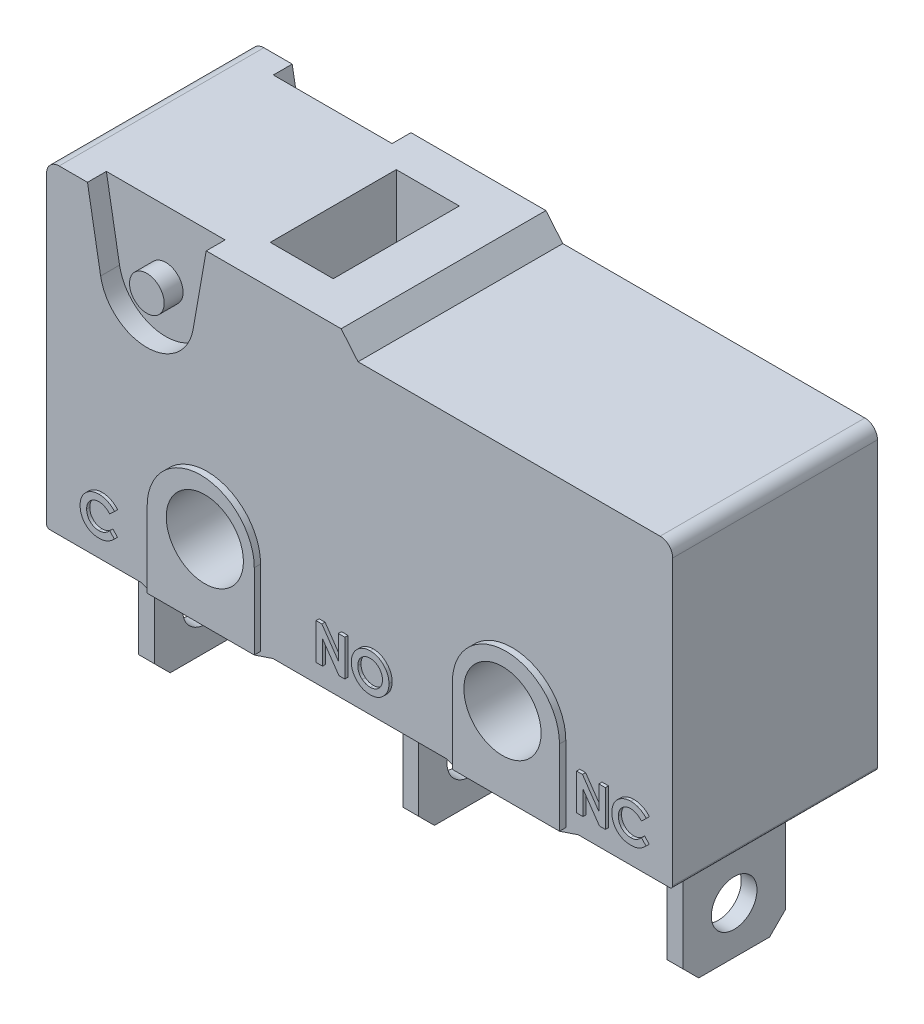
SolidWorks part; units mm, degrees
ref_plane "Front Plane" through (0, 0, 0) normal (0, 0, 1) x (1, 0, 0)
ref_plane "Top Plane" through (0, 0, 0) normal (0, 1, 0) x (1, 0, 0)
ref_plane "Right Plane" through (0, 0, 0) normal (1, 0, 0) x (0, 0, -1)
sketch "Sketch1" plane through (0, 0, 0) normal (0, 0, 1) x (1, 0, 0)
  line L0 (9.353, 0) -> (9.89, -0.64)
  line L1 (0.4, 0) -> (9.353, 0)
  line L2 (0, -0.4) -> (0, -10.15)
  line L3 (0, -10.15) -> (3, -10.15)
  line L4 (19.88, -1.04) -> (19.88, -10.15)
  line L5 (9.89, -0.64) -> (19.48, -0.64)
  line L6 (3, -10.15) -> (3.595, -10.35)
  line L7 (3.595, -10.35) -> (6.595, -10.35)
  line L8 (6.595, -10.35) -> (7.19, -10.15)
  line L9 (12.69, -10.15) -> (13.285, -10.35)
  line L10 (13.285, -10.35) -> (16.285, -10.35)
  line L11 (16.285, -10.35) -> (16.88, -10.15)
  line L12 (7.19, -10.15) -> (12.69, -10.15)
  line L13 (16.88, -10.15) -> (19.88, -10.15)
  arc A0 (0.4, 0) -> (0, -0.4) centre (0.4, -0.4) ccw
  arc A1 (19.48, -0.64) -> (19.88, -1.04) centre (19.48, -1.04) cw
  point P10 (0, 0)
  dimension "D1" = 0.4
  dimension "D2" = 10.15
  dimension "D3" = 9.51
  dimension "D4" = 9.89
  dimension "D5" = 130
  dimension "D6" = 19.88
  dimension "D7" = 3
  dimension "D8" = 3
  dimension "D9" = 3
  dimension "D10" = 5.5
  dimension "D11" = 0.2
extrude "Boss-Extrude1" add sketch "Sketch1" along normal blind 6.5
sketch "Sketch3" plane through (0, 0, 6.5) normal (0, 0, 1) x (1, 0, 0)
  line L0 (3.395, -7.75) -> (3.395, -10.15)
  line L1 (3.395, -10.15) -> (6.795, -10.15)
  line L2 (6.795, -10.15) -> (6.795, -7.75)
  line L3 (3.595, -10.35) -> (6.595, -10.35) construction
  line L4 (5.095, -6.05) -> (14.785, -6.05) construction
  line L5 (7.19, -10.15) -> (12.69, -10.15) construction
  line L6 (13.085, -7.75) -> (13.085, -10.15)
  line L7 (13.085, -10.15) -> (16.485, -10.15)
  line L8 (16.485, -10.15) -> (16.485, -7.75)
  line L9 (13.285, -10.35) -> (16.285, -10.35) construction
  arc A0 (3.395, -7.75) -> (6.795, -7.75) centre (5.095, -7.75) cw
  arc A1 (13.085, -7.75) -> (16.485, -7.75) centre (14.785, -7.75) cw
  point P5 (5.095, -10.15)
  point P6 (5.095, -10.35)
  point P18 (14.785, -10.35)
  point P19 (14.785, -10.15)
  dimension "D1" = 3.4
  dimension "D2" = 4.1
extrude "Boss-Extrude2" add sketch "Sketch3" along normal blind 0.2
ref_plane "Plane1" through (0, 0, 3.25) normal (0, 0, 1) x (1, 0, 0)
mirror "Mirror1" about plane through (0, 0, 3.25) normal (0, 0, 1) of "Boss-Extrude2"
sketch "Sketch4" plane through (0, 0, 6.7) normal (0, 0, 1) x (1, 0, 0)
  circle A0 centre (5.2252, -7.7506) radius 1.225
  circle A1 centre (14.6752, -7.75) radius 1.225
  dimension "D1" = 2.45
  dimension "D2" = 9.45
extrude "Cut-Extrude1" cut sketch "Sketch4" against normal blind 10.2
fillet "Fillet1" radius 0.1 2 edges at (19.88, -10.15, 3.25) (0, -10.15, 3.25)
sketch "Sketch5" plane through (0, 0, 6.5) normal (0, 0, 1) x (1, 0, 0)
  line L0 (1.7177, -2.3688) -> (1.3, 0)
  line L1 (9.353, 0) -> (0.4, 0) construction
  line L2 (4.6523, -2.3688) -> (5.07, 0)
  line L3 (3.185, -3.6) -> (0, -3.6) construction
  line L4 (0, -0.4) -> (0, -10.05) construction
  line L5 (1.3, 0) -> (5.07, 0)
  arc A0 (1.7177, -2.3688) -> (4.6523, -2.3688) centre (3.185, -2.11) ccw
  circle A1 centre (3.185, -2.11) radius 0.55
  dimension "D5" = 1.1
  dimension "D1" = 3.6
  dimension "D2" = 1.3
  dimension "D3" = 3.77
  dimension "D4" = 100
extrude "Cut-Extrude2" cut sketch "Sketch5" against normal blind 0.6
mirror "Mirror2" about plane through (0, 0, 3.25) normal (0, 0, 1) of "Cut-Extrude2"
sketch "Sketch6" plane through (0, 0, 0) normal (0, 1, 0) x (1, 0, 0)
  line L0 (9.353, -6.5) -> (9.353, 0) construction
  line L1 (5.853, -1.25) -> (7.853, -1.25)
  line L2 (5.853, -1.25) -> (5.853, -5.25)
  line L3 (5.853, -5.25) -> (7.853, -5.25)
  line L4 (7.853, -1.25) -> (7.853, -5.25)
  point P4 (9.353, -3.25)
  point P5 (7.853, -3.25)
  dimension "D1" = 2
  dimension "D2" = 4
  dimension "D3" = 1.5
extrude "Cut-Extrude3" cut sketch "Sketch6" against normal blind 2
sketch "Sketch7" plane through (0, -10.15, 0) normal (0, -1, 0) x (1, 0, 0)
  line L0 (0.1, 6.5) -> (3, 6.5) construction
  line L1 (1.3, 4.875) -> (1.8, 4.875)
  line L2 (1.3, 4.875) -> (1.3, 1.625)
  line L3 (1.3, 1.625) -> (1.8, 1.625)
  line L4 (1.8, 4.875) -> (1.8, 1.625)
  line L5 (9.69, 4.875) -> (10.19, 4.875)
  line L6 (9.69, 4.875) -> (9.69, 1.625)
  line L7 (9.69, 1.625) -> (10.19, 1.625)
  line L8 (10.19, 4.875) -> (10.19, 1.625)
  line L9 (18.08, 4.875) -> (18.58, 4.875)
  line L10 (18.08, 4.875) -> (18.08, 1.625)
  line L11 (18.08, 1.625) -> (18.58, 1.625)
  line L12 (18.58, 4.875) -> (18.58, 1.625)
  line L13 (7.19, 6.5) -> (12.69, 6.5) construction
  line L14 (16.88, 6.5) -> (19.78, 6.5) construction
  line L15 (3, 6.5) -> (3, 0) construction
  point P12 (1.55, 6.5)
  point P13 (1.55, 4.875)
  point P16 (9.94, 4.875)
  point P17 (9.94, 6.5)
  point P18 (18.33, 4.875)
  point P21 (18.33, 6.5)
  point P22 (3, 3.25)
  point P25 (1.8, 3.25)
  point P28 (9.69, 3.25)
  point P29 (18.08, 3.25)
  dimension "D1" = 3.25
  dimension "D2" = 0.5
extrude "Boss-Extrude3" add sketch "Sketch7" along normal blind 4.15
chamfer "Chamfer1" distance 0.5 angle 45 6 edges at (1.55, -14.3, 4.875) (9.94, -14.3, 4.875) (18.33, -14.3, 4.875) (18.33, -14.3, 1.625) (9.94, -14.3, 1.625) (1.55, -14.3, 1.625)
sketch "Sketch8" plane through (1.3, 0, 0) normal (-1, 0, 0) x (0, 0, 1)
  line L0 (4.375, -14.3) -> (2.125, -14.3) construction
  circle A0 centre (3.25, -12.8) radius 0.725
  point P2 (3.25, -14.3)
  dimension "D1" = 1.45
  dimension "D2" = 1.5
extrude "Cut-Extrude4" cut sketch "Sketch8" against normal blind 18.15
sketch "Sketch9" plane through (0, 0, 6.5) normal (0, 0, 1) x (1, 0, 0)
  text T0 "C              NO             NC" font "Century Gothic" height 1.15
extrude "Boss-Extrude4" add sketch "Sketch9" along normal blind 0.1
sketch "Sketch11" plane through (0, 0, 0) normal (0, 0, -1) x (-1, 0, 0)
  text T0 "KW       CE" font "Century Gothic" height 1.78
extrude "Boss-Extrude5" add sketch "Sketch11" along normal blind 0.1
sketch "Sketch12" plane through (0, 0, 0) normal (0, 0, -1) x (-1, 0, 0)
  text T0 "5A  125  250V" font "Century Gothic" height 1.3
extrude "Boss-Extrude6" add sketch "Sketch12" along normal blind 0.1
sketch "Sketch13" plane through (0, 0, 0) normal (0, 0, -1) x (-1, 0, 0)
  text T0 "2                  3                  1" font "Century Gothic" height 1.1
extrude "Boss-Extrude7" add sketch "Sketch13" along normal blind 0.1
sketch "Sketch14" plane through (0, 0, 0) normal (0, 0, -1) x (-1, 0, 0)
  line L0 (-18.2761, -7.6793) -> (-18.2761, -5.3079)
  line L1 (-18.2761, -5.3079) -> (-9.8134, -5.3079)
  line L2 (-9.8134, -5.3079) -> (-9.8134, -5.5774)
  line L3 (-9.8134, -7.7817) -> (-9.8134, -6.3917)
  line L4 (-3.5611, -6.0907) -> (-1.3125, -6.0907)
  line L5 (-1.3125, -6.0907) -> (-1.3125, -7.532)
  line L6 (-1.3125, -7.532) -> (-1.3625, -7.532)
  line L7 (-1.3625, -7.532) -> (-1.3625, -6.1407)
  line L8 (-1.3625, -6.1407) -> (-3.5611, -6.1407)
  line L9 (-3.5611, -6.1407) -> (-3.5611, -6.0907)
  line L10 (-18.2761, -7.6793) -> (-18.2261, -7.6793)
  line L11 (-18.2261, -7.6793) -> (-18.2261, -5.3579)
  line L12 (-18.2261, -5.3579) -> (-9.8634, -5.3579)
  line L13 (-9.8634, -5.3579) -> (-9.8634, -5.5774)
  line L14 (-9.8634, -5.5774) -> (-10.0384, -5.5774)
  line L15 (-10.0384, -5.5774) -> (-9.8384, -5.7774)
  line L16 (-9.8384, -5.7774) -> (-9.6384, -5.5774)
  line L17 (-9.6384, -5.5774) -> (-9.8134, -5.5774)
  line L18 (-9.8134, -7.7817) -> (-9.8634, -7.7817)
  line L19 (-9.8634, -7.7817) -> (-9.8634, -6.3917)
  line L20 (-9.8634, -6.3917) -> (-10.0384, -6.3917)
  line L21 (-10.0384, -6.3917) -> (-9.8384, -6.1917)
  line L22 (-9.8384, -6.1917) -> (-9.6384, -6.3917)
  line L23 (-9.6384, -6.3917) -> (-9.8134, -6.3917)
  line L24 (-9.8634, -5.3079) -> (-9.8634, -5.3579) construction
  line L25 (-9.8634, -5.3579) -> (-9.8134, -5.3579) construction
  line L26 (-9.8384, -6.0124) -> (-8.7652, -6.1417)
  line L27 (-8.7652, -6.1417) -> (-7.7787, -6.1417)
  line L28 (-7.7787, -6.1417) -> (-7.7787, -6.1917)
  line L29 (-7.7787, -6.1917) -> (-8.7652, -6.1917)
  line L30 (-8.7652, -6.1917) -> (-9.8384, -6.0624)
  line L31 (-9.8384, -6.0624) -> (-9.8384, -6.0124)
  line L32 (-9.8634, -5.5774) -> (-9.8134, -5.5774) construction
  point P28 (-9.8384, -5.5774)
  dimension "D1" = 0.05
  dimension "D2" = 0.05
  dimension "D3" = 0.2
  dimension "D4" = 0.2
extrude "Boss-Extrude8" add sketch "Sketch14" along normal blind 0.1
sketch "Sketch15" plane through (0, 0, 0) normal (0, 0, -1) x (-1, 0, 0)
  line L0 (-5.9919, -3.9223) -> (-5.0693, -3.2965) construction
  line L1 (-5.0693, -3.2965) -> (-5.0693, -4.5481) construction
  line L2 (-5.0693, -4.5481) -> (-4.1468, -3.9223) construction
  line L4 (-5.9919, -4.0227) -> (-5.0693, -3.3969) construction
  line L5 (-5.0693, -3.3969) -> (-5.0693, -4.6486) construction
  line L6 (-5.0693, -4.6486) -> (-4.1468, -4.0227) construction
  line L7 (-4.1468, -3.9223) -> (-4.1468, -4.0227)
  line L8 (-5.9919, -3.9223) -> (-5.9919, -4.0227)
  spline S0 degree 3 poles (-5.9919, -3.9223) (-5.0693, -3.2965) (-5.0693, -4.5481) (-4.1468, -3.9223) knots 0 0 0 0 1 1 1 1
  spline S1 degree 3 poles (-5.9919, -4.0227) (-5.0693, -3.3969) (-5.0693, -4.6486) (-4.1468, -4.0227) knots 0 0 0 0 1 1 1 1
  dimension "D1" = 0.1004
extrude "Boss-Extrude9" add sketch "Sketch15" along normal blind 0.1
ref_plane "Plane2" through (0, 0, 3.25) normal (0, 0, -1) x (-1, 0, 0)
sketch "Sketch17" plane through (18.58, 0, 0) normal (1, 0, 0) x (0, 0, -1)
  circle A0 centre (-3.25, -12.8) radius 0.725
extrude "Boss-Extrude11" [suppressed] add sketch "Sketch17" against normal blind 3 and the other way blind 1
sketch "Sketch18" [suppressed] plane through (1.8, 0, 0) normal (1, 0, 0) x (0, 0, -1)
  circle A0 centre (-3.25, -12.8) radius 0.725
extrude "Boss-Extrude12" [suppressed] add sketch "Sketch18" against normal blind 3 and the other way blind 1
other "1_0" parameters "Diameter"=1, "StubLength"=1.5
ref_axis "Axis2" through (28.58, -12.8, 3.25) along (-1, 0, 0)
other "0_0" parameters "Diameter"=1, "StubLength"=1.5
ref_axis "Axis3" through (11.8, -12.8, 3.25) along (-1, 0, 0)
